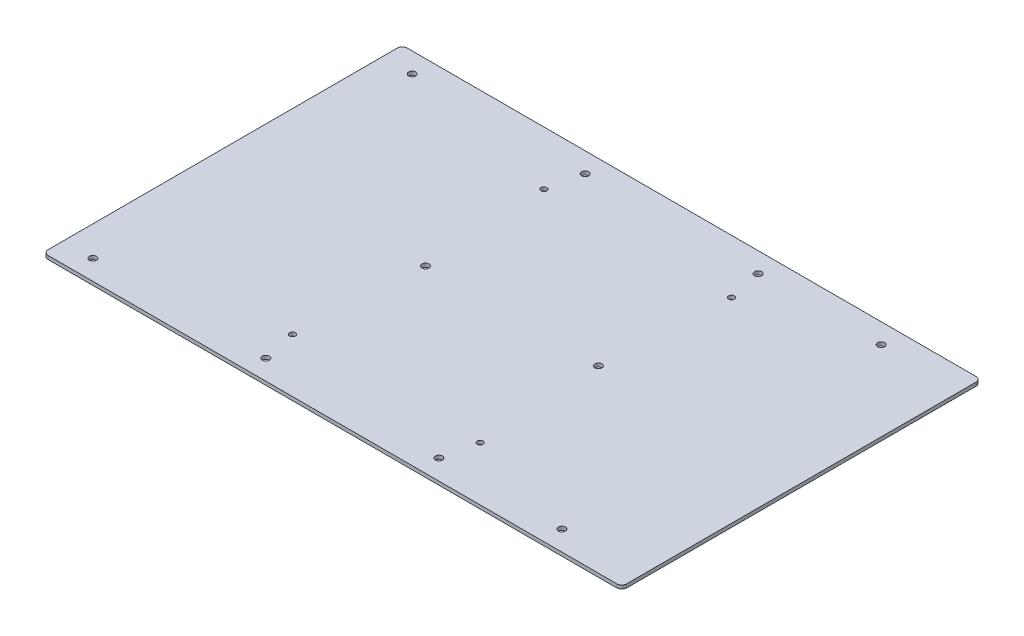
SolidWorks part; units mm, degrees
material "1060 Alloy"
ref_plane "Front" through (0, 0, 0) normal (0, 0, 1) x (1, 0, 0)
ref_plane "Top" through (0, 0, 0) normal (0, 1, 0) x (1, 0, 0)
ref_plane "Right" through (0, 0, 0) normal (1, 0, 0) x (0, 0, -1)
sketch "Sketch1" plane through (0, 0, 0) normal (0, 1, 0) x (1, 0, 0)
  line L0 (-55.0333, 0) -> (-165.1, 0) construction
  line L1 (-180.975, 114.3) -> (180.975, 114.3)
  line L2 (-184.15, 111.125) -> (-184.15, -111.125)
  line L3 (-180.975, -114.3) -> (180.975, -114.3)
  line L4 (184.15, 111.125) -> (184.15, -111.125)
  line L5 (-184.15, 114.3) -> (184.15, -114.3) construction
  line L6 (-184.15, -114.3) -> (184.15, 114.3) construction
  line L7 (-165.1, -101.6) -> (165.1, -101.6) construction
  line L8 (-165.1, -101.6) -> (-165.1, 101.6) construction
  line L9 (-165.1, 101.6) -> (165.1, 101.6) construction
  line L10 (165.1, -101.6) -> (165.1, 101.6) construction
  line L11 (-165.1, -101.6) -> (165.1, 101.6) construction
  line L12 (-165.1, 101.6) -> (165.1, -101.6) construction
  line L13 (-55.0333, -101.6) -> (55.0333, -101.6) construction
  line L14 (-55.0333, -101.6) -> (-55.0333, 101.6) construction
  line L15 (-55.0333, 101.6) -> (55.0333, 101.6) construction
  line L16 (55.0333, -101.6) -> (55.0333, 101.6) construction
  line L17 (-55.0333, -101.6) -> (55.0333, 101.6) construction
  line L18 (-55.0333, 101.6) -> (55.0333, -101.6) construction
  line L19 (55.0333, 0) -> (165.1, 0) construction
  line L20 (-55.0333, 0) -> (55.0333, 0) construction
  line L31 (-59.69, 80.01) -> (59.69, 80.01) construction
  line L32 (133.35, -101.6) -> (133.35, 101.6) construction
  line L33 (-59.69, 80.01) -> (-59.69, -80.01) construction
  line L34 (-59.69, -80.01) -> (59.69, -80.01) construction
  line L35 (59.69, 80.01) -> (59.69, -80.01) construction
  line L36 (-59.69, 80.01) -> (59.69, -80.01) construction
  line L37 (-59.69, -80.01) -> (59.69, 80.01) construction
  circle A0 centre (-165.1, 101.6) radius 2.2479
  circle A1 centre (-55.0333, 101.6) radius 2.2479
  circle A2 centre (55.0333, 101.6) radius 2.2479
  circle A3 centre (165.1, 101.6) radius 2.2479 construction
  circle A4 centre (165.1, -101.6) radius 2.2479 construction
  circle A5 centre (55.0333, -101.6) radius 2.2479
  circle A6 centre (-55.0333, -101.6) radius 2.2479
  circle A7 centre (-165.1, -101.6) radius 2.2479
  circle A12 centre (-55.0333, 0) radius 2.2479
  circle A13 centre (55.0333, 0) radius 2.2479
  arc A14 (184.15, 111.125) -> (180.975, 114.3) centre (180.975, 111.125) ccw
  arc A15 (184.15, -111.125) -> (180.975, -114.3) centre (180.975, -111.125) cw
  arc A16 (-180.975, -114.3) -> (-184.15, -111.125) centre (-180.975, -111.125) cw
  arc A17 (-180.975, 114.3) -> (-184.15, 111.125) centre (-180.975, 111.125) ccw
  circle A24 centre (133.35, -101.6) radius 2.2479
  circle A25 centre (133.35, 101.6) radius 2.2479
  circle A26 centre (59.69, -80.01) radius 1.8288
  circle A27 centre (-59.69, -80.01) radius 1.8288
  circle A28 centre (-59.69, 80.01) radius 1.8288
  circle A29 centre (59.69, 80.01) radius 1.8288
  point P0 (0, 0)
  point P6 (0, 0)
  point P11 (0, 0)
  point P28 (0, 0)
  point P29 (0, 0)
  point P30 (59.7864, 80.01)
  point P31 (59.7864, 80.01)
  point P32 (0, 0)
  point P55 (0, 0)
  point P59 (0, 0)
  point P60 (55.0333, 0)
  point P61 (59.7864, 80.01)
  point P64 (59.7864, 80.01)
  dimension "D5" = 4.4958
  dimension "D8" = 3.6576
  dimension "D11" = 3.175
  dimension "D1" = 368.3
  dimension "D2" = 228.6
  dimension "D3" = 12.7
  dimension "D4" = 19.05
  dimension "D6" = 160.02
  dimension "D7" = 50.8
  dimension "D9" = 119.38
extrude "Boss-Extrude1" add sketch "Sketch1" along normal blind 2.286
